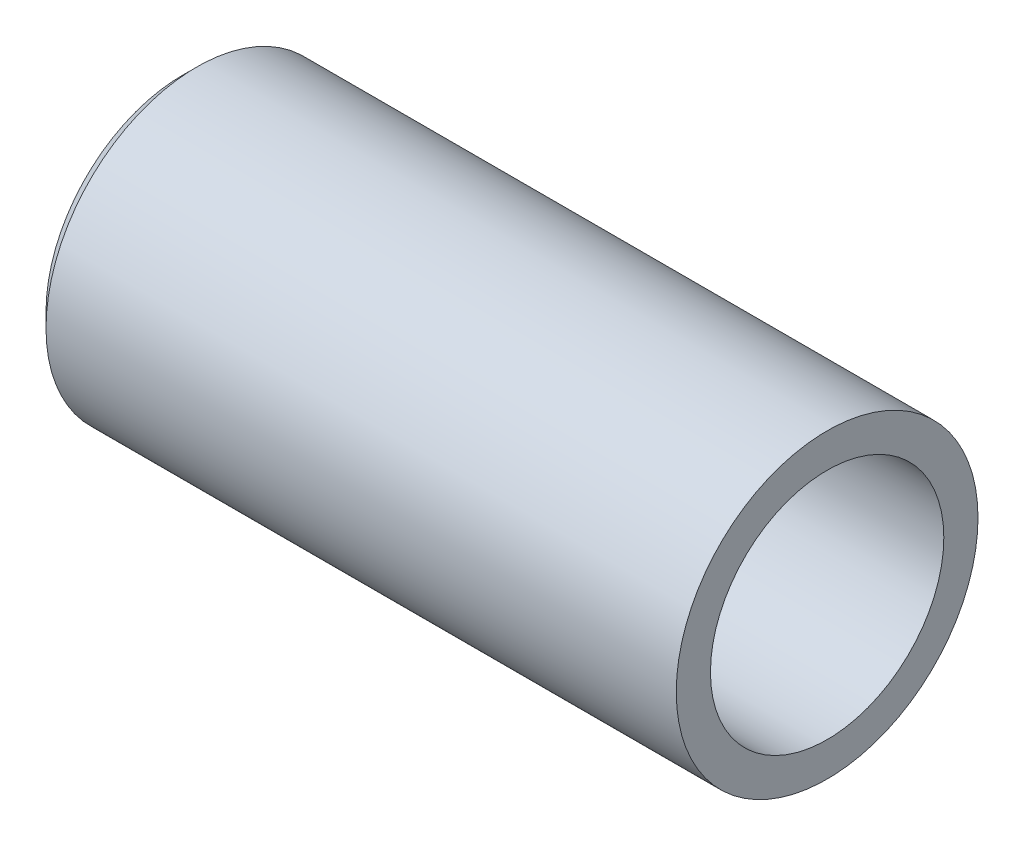
SolidWorks part; units mm, degrees
material "6061-T6 (SS)"
ref_plane "Front Plane" through (0, 0, 0) normal (0, 0, 1) x (1, 0, 0)
ref_plane "Top Plane" through (0, 0, 0) normal (0, 1, 0) x (1, 0, 0)
ref_plane "Right Plane" through (0, 0, 0) normal (1, 0, 0) x (0, 0, -1)
sketch "Sketch1" plane through (0, 0, 0) normal (0, 0, 1) x (1, 0, 0)
  line L0 (0, 0) -> (22.1407, 0) construction
  line L1 (0.9939, 5.2957) -> (23.1179, 5.2957)
  line L3 (0.4969, 4.0957) -> (23.1179, 4.0958)
  line L4 (23.3719, 5.2957) -> (23.3719, 1.3364) construction
  line L5 (23.1179, 5.2957) -> (23.1179, 4.0958)
  line L8 (0.4969, 4.0957) -> (0.4969, 4.7987)
  line L9 (0.4969, 4.7987) -> (0.9939, 5.2957)
  line L15 (0.4969, -7.9375) -> (0.4969, 7.9375) construction
  line L16 (23.3719, 14.4477) -> (23.3719, 18.245) construction
  dimension "D4" = 45
  dimension "D2" = 1.2
  dimension "D3" = 0.254
  dimension "D1" = 8.1915
revolve "Revolve1" add sketch "Sketch1" angle 360 about L0
equation "\"D2@Sketch1\"=1.2mm"
equation "\"D1@Sketch1\"=5/16 + 0.01"
